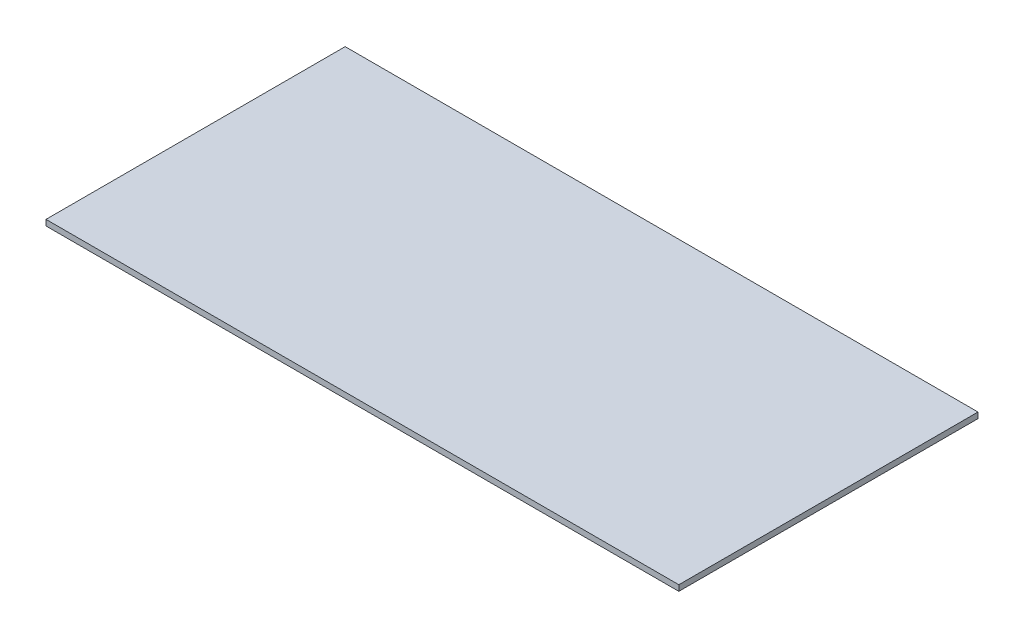
SolidWorks part; units mm, degrees
ref_plane "正面" through (0, 0, 0) normal (0, 0, 1) x (1, 0, 0)
ref_plane "平面" through (0, 0, 0) normal (0, 1, 0) x (1, 0, 0)
ref_plane "右側面" through (0, 0, 0) normal (1, 0, 0) x (0, 0, -1)
sketch "ｽｹｯﾁ1" plane through (0, 0, 0) normal (0, 1, 0) x (1, 0, 0)
  line L1 (-275, 130) -> (275, 130)
  line L2 (-275, 130) -> (-275, -130)
  line L3 (-275, -130) -> (275, -130)
  line L4 (275, 130) -> (275, -130)
  line L5 (-275, 130) -> (275, -130) construction
  line L6 (-275, -130) -> (275, 130) construction
  point P0 (0, 0)
  dimension "D1" = 260
  dimension "D2" = 550
extrude "ﾎﾞｽ - 押し出し1" add sketch "ｽｹｯﾁ1" along normal blind 5
